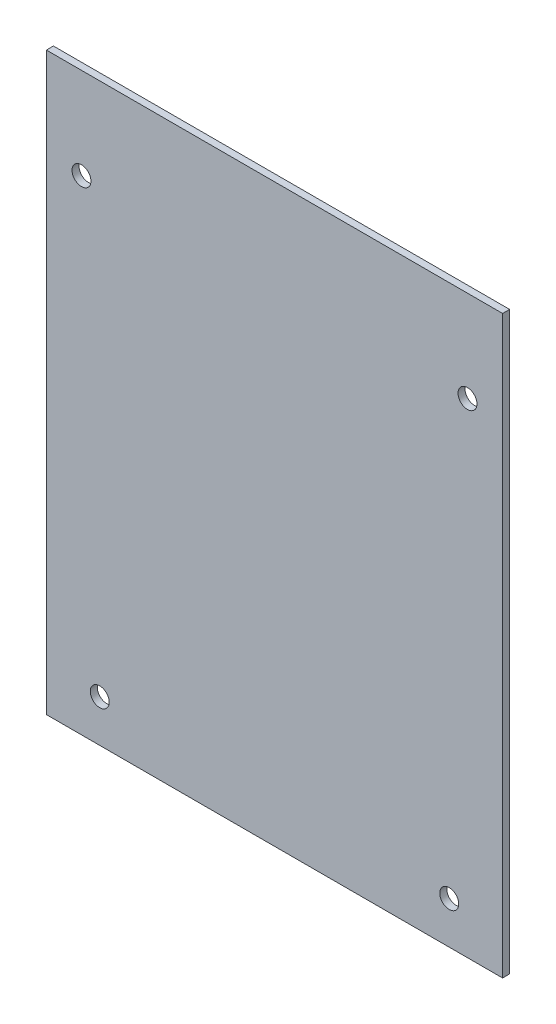
SolidWorks part; units mm, degrees
ref_plane "Alzado" through (0, 0, 0) normal (0, 0, 1) x (1, 0, 0)
ref_plane "Planta" through (0, 0, 0) normal (0, 1, 0) x (1, 0, 0)
ref_plane "Vista lateral" through (0, 0, 0) normal (1, 0, 0) x (0, 0, -1)
sketch "Croquis1" plane through (0, 0, 0) normal (0, 0, 1) x (1, 0, 0)
  line L1 (0, 82) -> (65, 82)
  line L2 (0, 82) -> (0, 0)
  line L3 (0, 0) -> (65, 0)
  line L4 (65, 82) -> (65, 0)
  dimension "D1" = 65
  dimension "D2" = 82
extrude "Saliente-Extruir1" add sketch "Croquis1" along normal blind 1
sketch "Croquis7" plane through (0, 0, 1) normal (0, 0, 1) x (1, 0, 0)
  line L0 (0, 6) -> (65, 6) construction
  line L1 (0, 82) -> (0, 0) construction
  line L2 (65, 0) -> (65, 82) construction
  line L3 (65, 69) -> (0, 69) construction
  line L4 (5, 0) -> (5, 82) construction
  line L5 (0, 0) -> (65, 0) construction
  line L6 (65, 82) -> (0, 82) construction
  line L7 (7.6, 0) -> (7.6, 82) construction
  line L8 (57.4, 0) -> (57.4, 82) construction
  line L9 (60, 0) -> (60, 82) construction
  line L10 (32.5, 82) -> (32.5, 0) construction
  dimension "D1" = 13
  dimension "D2" = 6
  dimension "D3" = 7.6
  dimension "D4" = 7.6
  dimension "D5" = 5
  dimension "D6" = 5
  dimension "D7" = 24.9
  dimension "D8" = 24.9
  dimension "D9" = 27.5
  dimension "D10" = 27.5
hole_wizard "Taladro de margen para M2.51" positions "Croquis3D6" profile "Croquis8" hole size "M2.5" standard "ISO" end condition through all
sketch3d "Croquis3D6"
  line L0 (65, 69, 1) -> (0, 69, 1) construction
  line L1 (5, 0, 1) -> (5, 82, 1) construction
  line L2 (60, 0, 1) -> (60, 82, 1) construction
  line L3 (0, 6, 1) -> (65, 6, 1) construction
  line L4 (7.6, 0, 1) -> (7.6, 82, 1) construction
  line L5 (57.4, 0, 1) -> (57.4, 82, 1) construction
  point P0 (5, 69, 1)
  point P6 (60, 69, 1)
  point P10 (7.6, 6, 1)
  point P16 (57.4, 6, 1)
sketch "Croquis8" plane through (5, 69, 1) normal (1, 0, 0) x (0, -1, 0)
  line L0 (0, 0) -> (0, 1)
  line L1 (0, 1) -> (1.35, 1)
  line L2 (1.35, 1) -> (1.35, 0)
  line L5 (1.35, 0) -> (0, 0)
  line L11 (0, -6.35) -> (0, 107.95) construction
  dimension "Diámetro de taladro hasta el siguiente" = 2.7
  dimension "Profundidad de taladro hasta el siguiente" = 1
